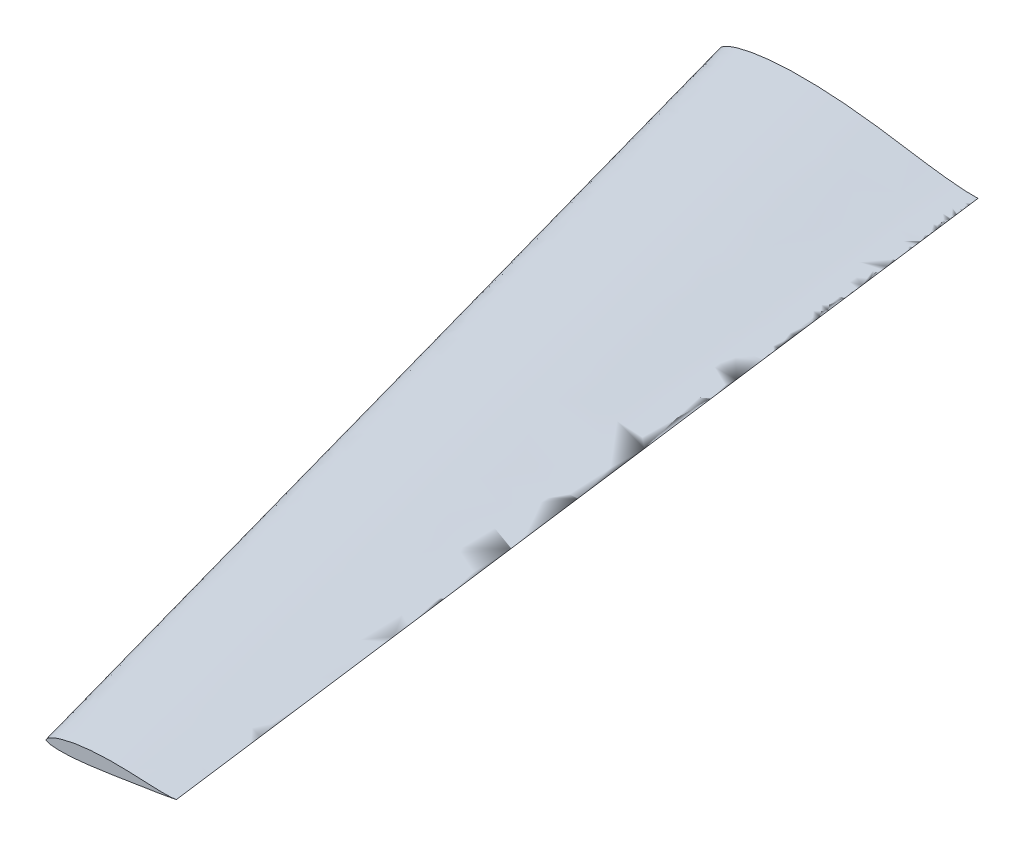
SolidWorks part; units mm, degrees
ref_plane "Front Plane" through (0, 0, 0) normal (0, 0, 1) x (1, 0, 0)
ref_plane "Top Plane" through (0, 0, 0) normal (0, 1, 0) x (1, 0, 0)
ref_plane "Right Plane" through (0, 0, 0) normal (1, 0, 0) x (0, 0, -1)
curve "Curve1"
  spline degree 3 poles (89.4117, -0.0768, 0) (90.1581, 0.0163, 0) (89.3384, -0.0489, 0) (88.6634, -0.0554, 0) (86.9988, -0.0528, 0) (84.9698, 0.0523, 0) (82.3441, 0.2429, 0) (79.2951, 0.5513, 0) (75.8494, 0.9741, 0) (72.0904, 1.4967, 0) (68.0818, 2.0963, 0) (63.8898, 2.7454, 0) (59.5721, 3.4086, 0) (55.1731, 4.0377, 0) (50.7294, 4.6, 0) (46.2733, 5.0781, 0) (41.8379, 5.4578, 0) (37.4583, 5.7341, 0) (33.171, 5.903, 0) (29.014, 5.9637, 0) (25.0243, 5.916, 0) (21.2371, 5.7575, 0) (17.6835, 5.491, 0) (14.3911, 5.12, 0) (11.385, 4.6544, 0) (8.6886, 4.1134, 0) (6.3249, 3.5134, 0) (4.3152, 2.87, 0) (2.6751, 2.2019, 0) (1.4179, 1.5316, 0) (0.6259, 0.9504, 0) (0.2409, 0.5277, 0) (0.0946, 0.3023, 0) (0.0289, 0.1579, 0) (-0.0008, 0.0428, 0) (-0.0021, -0.0493, 0) (0.0369, -0.1348, 0) (0.1141, -0.2351, 0) (0.2404, -0.3544, 0) (0.4668, -0.5223, 0) (1.0037, -0.8427, 0) (2.0204, -1.2501, 0) (3.5765, -1.7042, 0) (5.5485, -2.1302, 0) (7.9154, -2.5093, 0) (10.6594, -2.8252, 0) (13.7595, -3.0666, 0) (17.1926, -3.2314, 0) (20.9311, -3.3172, 0) (24.9437, -3.3283, 0) (29.1943, -3.2696, 0) (33.6423, -3.153, 0) (38.2418, -2.9882, 0) (42.9422, -2.7897, 0) (47.6888, -2.5669, 0) (52.4251, -2.3307, 0) (57.0933, -2.0873, 0) (61.6364, -1.844, 0) (65.999, -1.6043, 0) (70.1278, -1.373, 0) (73.9729, -1.1522, 0) (77.4858, -0.9472, 0) (80.6263, -0.7576, 0) (83.3439, -0.5873, 0) (85.6375, -0.4302, 0) (87.3906, -0.2992, 0) (88.8126, -0.1608, 0) (89.4117, -0.0768, 0) (90.1581, 0.0163, 0) (89.3384, -0.0489, 0) knots -0.013312 -0.00609 -0.00158 0 0.001669 0.006747 0.015187 0.026742 0.041155 0.058129 0.077283 0.098227 0.12058 0.143966 0.168018 0.192451 0.217075 0.24171 0.266182 0.29031 0.313903 0.336767 0.358704 0.37954 0.399122 0.417322 0.434037 0.449154 0.462553 0.474139 0.483848 0.491647 0.497539 0.499898 0.501005 0.501951 0.502492 0.502956 0.503431 0.504004 0.505035 0.506276 0.508636 0.515301 0.524213 0.535296 0.548467 0.563638 0.580726 0.599619 0.62018 0.642246 0.665633 0.690118 0.715452 0.741354 0.76752 0.793634 0.819375 0.844429 0.868488 0.891259 0.912467 0.93185 0.949165 0.964196 0.976755 0.986688 0.99391 0.99842 1 1.001669 1.006747 1.015187 periodic
sketch "CentralProfile" plane through (0, 0, 0) normal (0, 0, 1) x (1, 0, 0)
  line L0 (90, 0) -> (-10, 0) construction
  spline S1 degree 3 poles (89.3464, -0.0853) (90.1757, 0.0181) (89.2649, -0.0544) (88.5149, -0.0616) (86.6653, -0.0586) (84.411, 0.0582) (81.4935, 0.27) (78.1057, 0.6128) (74.2772, 1.0827) (70.1005, 1.6634) (65.6465, 2.3298) (60.9889, 3.051) (56.1914, 3.7881) (51.3037, 4.4871) (46.3662, 5.112) (41.4151, 5.6433) (36.4869, 6.0653) (31.6207, 6.3724) (26.8571, 6.5601) (22.2382, 6.6277) (17.8052, 6.5747) (13.5972, 6.3988) (9.6488, 6.1027) (5.9906, 5.6906) (2.6505, 5.1733) (-0.3455, 4.5723) (-2.9718, 3.9057) (-5.2048, 3.1908) (-7.0272, 2.4486) (-8.4241, 1.7038) (-9.3042, 1.0581) (-9.7319, 0.5884) (-9.8945, 0.3379) (-9.9674, 0.1775) (-10.0005, 0.0496) (-10.0019, -0.0527) (-9.9586, -0.1477) (-9.8728, -0.2592) (-9.7325, -0.3918) (-9.481, -0.5783) (-8.8844, -0.9344) (-7.7548, -1.387) (-6.0258, -1.8916) (-3.8347, -2.365) (-1.2048, -2.7863) (1.844, -3.1373) (5.2887, -3.4056) (9.1032, -3.5888) (13.2571, -3.6842) (17.7154, -3.6966) (22.4383, -3.6314) (27.3806, -3.5021) (32.4911, -3.319) (37.7137, -3.0986) (42.9877, -2.8511) (48.2502, -2.5888) (53.4371, -2.3185) (58.485, -2.0483) (63.3323, -1.782) (67.9199, -1.5251) (72.1922, -1.2798) (76.0954, -1.0522) (79.5848, -0.8416) (82.6044, -0.6524) (85.1527, -0.4778) (87.1006, -0.3324) (88.6806, -0.1786) (89.3464, -0.0853) (90.1757, 0.0181) (89.2649, -0.0544) knots -0.013312 -0.00609 -0.00158 0 0.001669 0.006747 0.015187 0.026742 0.041155 0.058129 0.077283 0.098227 0.12058 0.143966 0.168018 0.192451 0.217075 0.24171 0.266182 0.29031 0.313903 0.336767 0.358704 0.37954 0.399122 0.417322 0.434037 0.449154 0.462553 0.474139 0.483848 0.491647 0.497539 0.499898 0.501005 0.501951 0.502492 0.502956 0.503431 0.504004 0.505035 0.506276 0.508636 0.515301 0.524213 0.535296 0.548467 0.563638 0.580726 0.599619 0.62018 0.642246 0.665633 0.690118 0.715452 0.741354 0.76752 0.793634 0.819375 0.844429 0.868488 0.891259 0.912467 0.93185 0.949165 0.964196 0.976755 0.986688 0.99391 0.99842 1 1.001669 1.006747 1.015187 only from (90, 0) to (90, 0)
  dimension "D1" = 100
ref_plane "CentralProfilePlane" through (0, 0, 0) normal (0, 0, 1) x (1, 0, 0)
curve "Curve2"
  spline degree 3 poles (49.6732, -0.0427, 360) (50.0878, 0.0091, 360) (49.6325, -0.0272, 360) (49.2574, -0.0308, 360) (48.3327, -0.0294, 360) (47.2055, 0.0291, 360) (45.7467, 0.1349, 360) (44.0528, 0.3063, 360) (42.1386, 0.5412, 360) (40.0502, 0.8315, 360) (37.8232, 1.1646, 360) (35.4944, 1.5252, 360) (33.0956, 1.8937, 360) (30.6517, 2.2432, 360) (28.183, 2.5556, 360) (25.7074, 2.8212, 360) (23.2433, 3.0321, 360) (20.8102, 3.1856, 360) (18.4283, 3.2794, 360) (16.1189, 3.3132, 360) (13.9024, 3.2866, 360) (11.7984, 3.1986, 360) (9.8242, 3.0505, 360) (7.9951, 2.8444, 360) (6.325, 2.5858, 360) (4.827, 2.2852, 360) (3.5139, 1.9519, 360) (2.3974, 1.5945, 360) (1.4862, 1.2233, 360) (0.7877, 0.8509, 360) (0.3477, 0.528, 360) (0.1338, 0.2932, 360) (0.0525, 0.1679, 360) (0.0161, 0.0877, 360) (-0.0005, 0.0238, 360) (-0.0012, -0.0274, 360) (0.0205, -0.0749, 360) (0.0634, -0.1306, 360) (0.1336, -0.1969, 360) (0.2593, -0.2902, 360) (0.5576, -0.4682, 360) (1.1224, -0.6945, 360) (1.9869, -0.9468, 360) (3.0825, -1.1835, 360) (4.3974, -1.3941, 360) (5.9219, -1.5695, 360) (7.6442, -1.7037, 360) (9.5515, -1.7952, 360) (11.6284, -1.8429, 360) (13.8576, -1.849, 360) (16.2191, -1.8164, 360) (18.6902, -1.7517, 360) (21.2455, -1.6601, 360) (23.8568, -1.5499, 360) (26.4938, -1.4261, 360) (29.125, -1.2948, 360) (31.7185, -1.1596, 360) (34.2425, -1.0245, 360) (36.6661, -0.8913, 360) (38.9599, -0.7628, 360) (41.0961, -0.6401, 360) (43.0477, -0.5262, 360) (44.7924, -0.4209, 360) (46.3022, -0.3263, 360) (47.5764, -0.239, 360) (48.5503, -0.1662, 360) (49.3403, -0.0893, 360) (49.6732, -0.0427, 360) (50.0878, 0.0091, 360) (49.6325, -0.0272, 360) knots -0.013312 -0.00609 -0.00158 0 0.001669 0.006747 0.015187 0.026742 0.041155 0.058129 0.077283 0.098227 0.12058 0.143966 0.168018 0.192451 0.217075 0.24171 0.266182 0.29031 0.313903 0.336767 0.358704 0.37954 0.399122 0.417322 0.434037 0.449154 0.462553 0.474139 0.483848 0.491647 0.497539 0.499898 0.501005 0.501951 0.502492 0.502956 0.503431 0.504004 0.505035 0.506276 0.508636 0.515301 0.524213 0.535296 0.548467 0.563638 0.580726 0.599619 0.62018 0.642246 0.665633 0.690118 0.715452 0.741354 0.76752 0.793634 0.819375 0.844429 0.868488 0.891259 0.912467 0.93185 0.949165 0.964196 0.976755 0.986688 0.99391 0.99842 1 1.001669 1.006747 1.015187 periodic
ref_plane "OutsideProfilePlane" through (0, 0, 360) normal (0, 0, 1) x (1, 0, 0)
sketch "OutsideProfile" plane through (0, 0, 360) normal (0, 0, 1) x (1, 0, 0)
  line L0 (139.8097, 3.4008) -> (90, -0.957) construction
  line L1 (0, 0) -> (97.907, 0) construction
  spline S1 degree 3 poles (139.4845, 3.3236) (139.8974, 3.4191) (139.4418, 3.335) (139.0638, 3.2922) (138.1307, 3.1971) (136.9874, 3.1384) (135.5047, 3.093) (133.7779, 3.089) (131.8221, 3.1262) (129.685, 3.2011) (127.4034, 3.3047) (125.0163, 3.4254) (122.5578, 3.5467) (120.0558, 3.6442) (117.5326, 3.7017) (115.0073, 3.7112) (112.4993, 3.6668) (110.0286, 3.5677) (107.6159, 3.4137) (105.2824, 3.2067) (103.0491, 2.9486) (100.9356, 2.6401) (98.9593, 2.2847) (97.1355, 1.8858) (95.4777, 1.4505) (93.9978, 0.991) (92.7077, 0.5176) (91.6187, 0.0404) (90.7381, -0.4291) (90.0724, -0.8777) (89.6622, -1.2494) (89.4709, -1.5086) (89.402, -1.6435) (89.3736, -1.7282) (89.3635, -1.7944) (89.3682, -1.8461) (89.395, -1.8918) (89.4441, -1.9436) (89.5218, -2.0031) (89.6584, -2.0841) (89.9779, -2.2325) (90.5714, -2.4019) (91.4699, -2.5662) (92.5998, -2.6906) (93.9484, -2.7658) (95.5047, -2.7837) (97.2563, -2.7392) (99.19, -2.6325) (101.2904, -2.4638) (103.54, -2.2373) (105.9189, -1.9579) (108.4052, -1.6346) (110.9736, -1.2755) (113.5965, -0.8917) (116.244, -0.4916) (118.8849, -0.0845) (121.4872, 0.3226) (124.0194, 0.7224) (126.4507, 1.1098) (128.7514, 1.4788) (130.8937, 1.8256) (132.8507, 2.1442) (134.5999, 2.4326) (136.1132, 2.6856) (137.3896, 2.9067) (138.3645, 3.0818) (139.1535, 3.2418) (139.4845, 3.3236) (139.8974, 3.4191) (139.4418, 3.335) knots -0.013312 -0.00609 -0.00158 0 0.001669 0.006747 0.015187 0.026742 0.041155 0.058129 0.077283 0.098227 0.12058 0.143966 0.168018 0.192451 0.217075 0.24171 0.266182 0.29031 0.313903 0.336767 0.358704 0.37954 0.399122 0.417322 0.434037 0.449154 0.462553 0.474139 0.483848 0.491647 0.497539 0.499898 0.501005 0.501951 0.502492 0.502956 0.503431 0.504004 0.505035 0.506276 0.508636 0.515301 0.524213 0.535296 0.548467 0.563638 0.580726 0.599619 0.62018 0.642246 0.665633 0.690118 0.715452 0.741354 0.76752 0.793634 0.819375 0.844429 0.868488 0.891259 0.912467 0.93185 0.949165 0.964196 0.976755 0.986688 0.99391 0.99842 1 1.001669 1.006747 1.015187 only from (139.8097, 3.4008) to (139.8097, 3.4008)
  point P1 (90, -0.957)
  dimension "D1" = 50
  dimension "D2" = 5
  dimension "D3" = 90
ref_axis "Axis3" through (-10, 0, 0) along (0.2676, -0.0026, 0.9635)
loft "Loft3" add profiles "OutsideProfile", "CentralProfile" connector at (89.3795, -1.8639, 360) connector at (-9.9991, -0.023, 0)
mirror "Mirror1" [suppressed] about plane through (0, 0, 0) normal (0, 0, 1)
